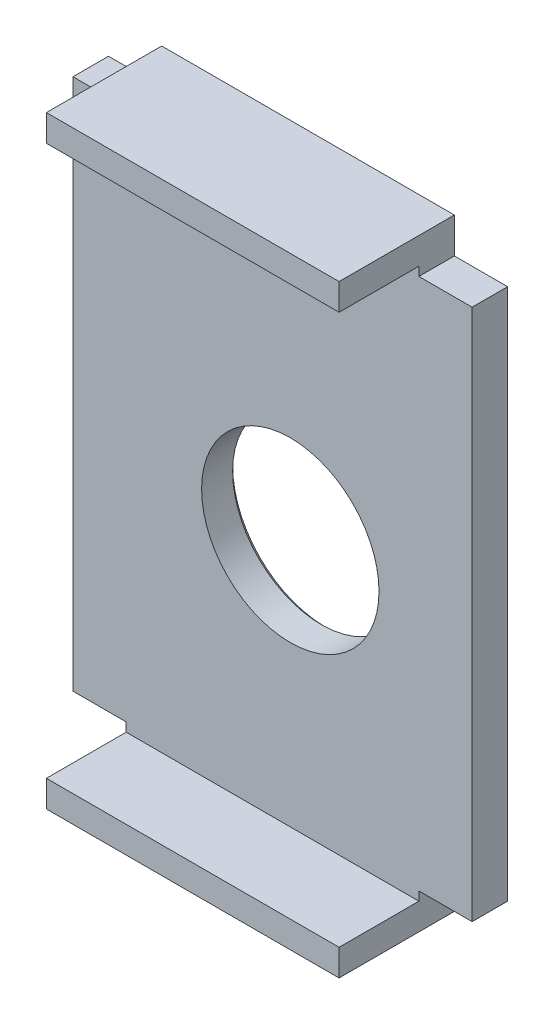
SolidWorks part; units mm, degrees
ref_plane "Front Plane" through (0, 0, 0) normal (0, 0, 1) x (1, 0, 0)
ref_plane "Top Plane" through (0, 0, 0) normal (0, 1, 0) x (1, 0, 0)
ref_plane "Right Plane" through (0, 0, 0) normal (1, 0, 0) x (0, 0, -1)
sketch "Sketch1" plane through (0, 0, 0) normal (0, 0, 1) x (1, 0, 0)
  line L5 (-22.5, -30) -> (22.5, -30)
  line L6 (-22.5, -30) -> (-22.5, 30)
  line L7 (-22.5, 30) -> (22.5, 30)
  line L8 (22.5, -30) -> (22.5, 30)
  line L9 (-22.5, -30) -> (22.5, 30) construction
  line L10 (-22.5, 30) -> (22.5, -30) construction
  circle A2 centre (2, -3) radius 10
  point P0 (0, 0)
  dimension "D3" = 20
  dimension "D1" = 60
  dimension "D2" = 45
  dimension "D4" = 20.5
  dimension "D5" = 3
extrude "Boss-Extrude1" add sketch "Sketch1" along normal mid plane 4
sketch "Sketch3" plane through (0, 0, -2) normal (0, 0, -1) x (-1, 0, 0)
  line L0 (-22.5, 30) -> (22.5, 30) construction
  line L1 (-16.5, 30) -> (16.5, 30)
  line L2 (-16.5, 30) -> (-16.5, 34)
  line L3 (-16.5, 34) -> (16.5, 34)
  line L4 (16.5, 30) -> (16.5, 34)
  line L5 (-22.5, -30) -> (-22.5, 30) construction
  line L6 (22.5, 30) -> (22.5, -30) construction
  line L7 (22.5, -30) -> (-22.5, -30) construction
  line L8 (-16.5, -30) -> (16.5, -30)
  line L9 (-16.5, -30) -> (-16.5, -34)
  line L10 (-16.5, -34) -> (16.5, -34)
  line L11 (16.5, -30) -> (16.5, -34)
  dimension "D1" = 6
  dimension "D2" = 6
  dimension "D3" = 4
extrude "Boss-Extrude3" add sketch "Sketch3" against normal blind 13
chamfer "Chamfer1" distance 0.5 angle 45 1 edges at (12, -3, -2)
sketch "Sketch4" plane through (0, 0, 11) normal (0, 0, 1) x (1, 0, 0)
  line L0 (16.5, 34) -> (16.5, 30) construction
  line L1 (-16.5, 30) -> (16.5, 30)
  line L2 (-16.5, 30) -> (-16.5, 31)
  line L3 (-16.5, 31) -> (16.5, 31)
  line L4 (16.5, 30) -> (16.5, 31)
  line L5 (-16.5, -34) -> (-16.5, -30) construction
  line L6 (16.5, -30) -> (-16.5, -30)
  line L7 (16.5, -30) -> (16.5, -31)
  line L8 (16.5, -31) -> (-16.5, -31)
  line L9 (-16.5, -30) -> (-16.5, -31)
  dimension "D1" = 1
extrude "Cut-Extrude1" cut sketch "Sketch4" against normal up to vertex (9 mm away) up to point (16.5, -30, 2)
equation "\"padding\"=6"
equation "\"wall_thick_ness\"=4"
equation "\"D1@Sketch3\"=\"padding\""
equation "\"D2@Sketch3\"=\"padding\""
equation "\"D3@Sketch3\"=\"wall_thick_ness\""
equation "\"D1@Boss-Extrude1\"=\"wall_thick_ness\""
